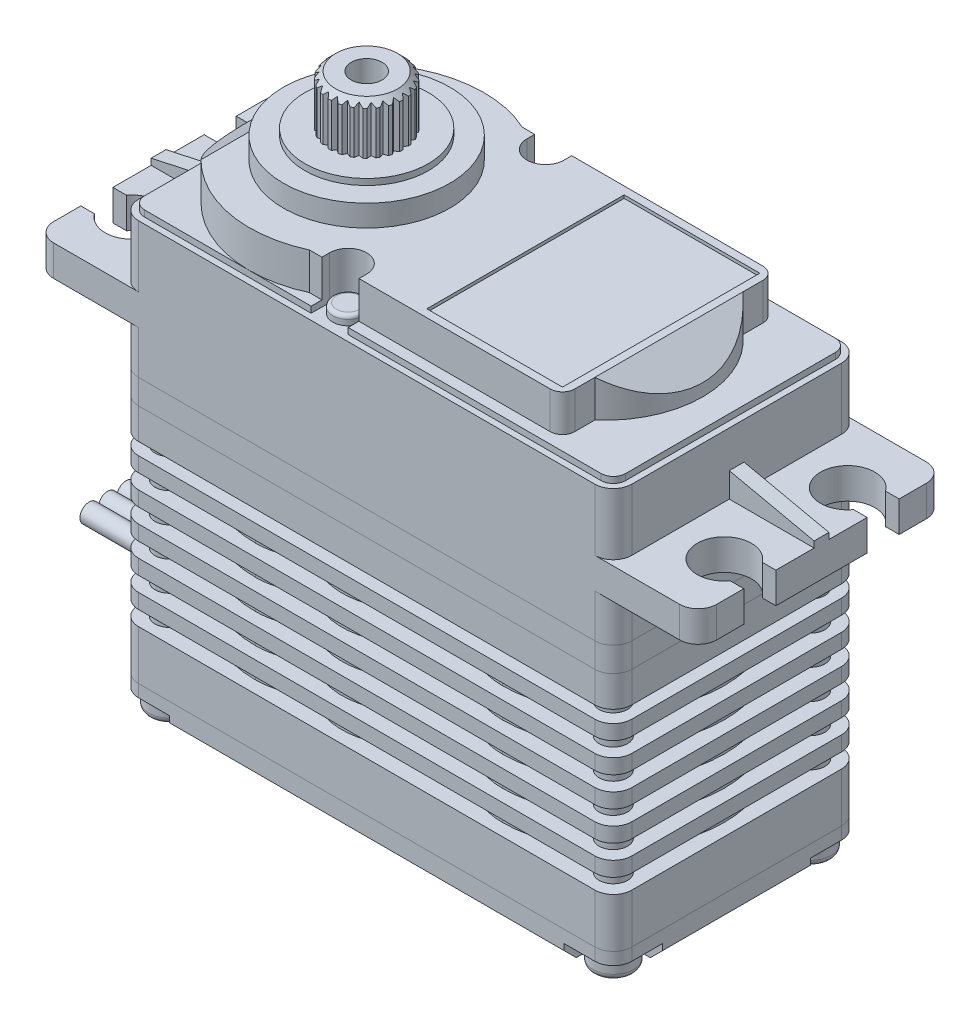
SolidWorks part; units mm, degrees
ref_plane "Front Plane" through (0, 0, 0) normal (0, 0, 1) x (1, 0, 0)
ref_plane "Top Plane" through (0, 0, 0) normal (0, 1, 0) x (1, 0, 0)
ref_plane "Right Plane" through (0, 0, 0) normal (1, 0, 0) x (0, 0, -1)
sketch "Sketch3" plane through (0, 0, 0) normal (0, 1, 0) x (1, 0, 0)
  line L1 (-20, -10) -> (20, -10)
  line L2 (-20, -10) -> (-20, 10)
  line L3 (-20, 10) -> (20, 10)
  line L4 (20, -10) -> (20, 10)
  line L5 (-20, -10) -> (20, 10) construction
  line L6 (-20, 10) -> (20, -10) construction
  point P0 (0, 0)
  dimension "D1" = 40
  dimension "D2" = 20
extrude "Boss-Extrude2" add sketch "Sketch3" against normal blind 27.5 and the other way blind 7.5
sketch "Sketch4" plane through (0, 0, 0) normal (0, 1, 0) x (1, 0, 0)
  line L0 (20, 10) -> (-20, 10) construction
  line L1 (-26.875, -10) -> (26.875, -10)
  line L2 (-26.875, -10) -> (-26.875, 10)
  line L3 (-26.875, 10) -> (26.875, 10)
  line L4 (26.875, -10) -> (26.875, 10)
  line L5 (-26.875, -10) -> (26.875, 10) construction
  line L6 (-26.875, 10) -> (26.875, -10) construction
  point P0 (0, 0)
  dimension "D1" = 53.75
extrude "Boss-Extrude3" add sketch "Sketch4" along normal blind 2.5
sketch "Sketch5" plane through (0, 2.5, 0) normal (0, 1, 0) x (1, 0, 0)
  line L1 (-24, -5) -> (24, -5) construction
  line L2 (-24, -5) -> (-24, 5) construction
  line L3 (-24, 5) -> (24, 5) construction
  line L4 (24, -5) -> (24, 5) construction
  line L5 (-24, -5) -> (24, 5) construction
  line L6 (-24, 5) -> (24, -5) construction
  circle A0 centre (-24, 5) radius 2.2
  circle A1 centre (-24, -5) radius 2.2
  circle A2 centre (24, -5) radius 2.2
  circle A3 centre (24, 5) radius 2.2
  point P0 (0, 0)
  dimension "D3" = 4.4
  dimension "D1" = 10
  dimension "D2" = 48
extrude "Cut-Extrude2" cut sketch "Sketch5" against normal through all
sketch "Sketch6" plane through (0, 2.5, 0) normal (0, 1, 0) x (1, 0, 0)
  line L0 (-24, 5) -> (-26.875, 5) construction
  line L1 (-26.875, 10) -> (-26.875, -10) construction
  line L2 (-24, 3.7) -> (-26.875, 3.7)
  line L3 (-24, 6.3) -> (-26.875, 6.3)
  line L4 (-24, -5) -> (-26.875, -5) construction
  line L5 (-24, -6.3) -> (-26.875, -6.3)
  line L6 (-24, -3.7) -> (-26.875, -3.7)
  line L7 (24, -5) -> (26.875, -5) construction
  line L8 (26.875, -10) -> (26.875, 10) construction
  line L9 (24, -3.7) -> (26.875, -3.7)
  line L10 (24, -6.3) -> (26.875, -6.3)
  line L11 (24, 5) -> (26.875, 5) construction
  line L12 (24, 6.3) -> (26.875, 6.3)
  line L13 (24, 3.7) -> (26.875, 3.7)
  arc A0 (-24, 3.7) -> (-24, 6.3) centre (-24, 5) ccw
  arc A1 (-26.875, 6.3) -> (-26.875, 3.7) centre (-26.875, 5) ccw
  arc A2 (-24, -6.3) -> (-24, -3.7) centre (-24, -5) ccw
  arc A3 (-26.875, -3.7) -> (-26.875, -6.3) centre (-26.875, -5) ccw
  arc A4 (24, -3.7) -> (24, -6.3) centre (24, -5) ccw
  arc A5 (26.875, -6.3) -> (26.875, -3.7) centre (26.875, -5) ccw
  arc A6 (24, 6.3) -> (24, 3.7) centre (24, 5) ccw
  arc A7 (26.875, 3.7) -> (26.875, 6.3) centre (26.875, 5) ccw
  point P5 (-25.4375, 5)
  point P10 (-25.4375, -5)
  point P18 (25.4375, -5)
  point P28 (25.4375, 5)
  dimension "D1" = 2.6
extrude "Cut-Extrude3" cut sketch "Sketch6" against normal through all
fillet "Fillet1" radius 1.5 4 edges at (26.875, 1.25, -10) (26.875, 1.25, 10) (-26.875, 1.25, 10) (-26.875, 1.25, -10)
fillet "Fillet2" radius 1.5 8 edges at (20, -13.75, -10) (20, 5, -10) (20, -13.75, 10) (20, 5, 10) (-20, 5, -10) (-20, -13.75, -10) (-20, 5, 10) (-20, -13.75, 10)
sketch "Sketch7" plane through (0, 7.5, 0) normal (0, 1, 0) x (1, 0, 0)
  line L8 (19.5, -8.5) -> (19.5, 8.5)
  line L9 (18.5, 9.5) -> (-18.5, 9.5)
  line L10 (-19.5, 8.5) -> (-19.5, -8.5)
  line L11 (-18.5, -9.5) -> (18.5, -9.5)
  line L12 (19.5, -8.5) -> (19.5, 8.5)
  line L13 (18.5, 9.5) -> (-18.5, 9.5)
  line L14 (-19.5, 8.5) -> (-19.5, -8.5)
  line L15 (-18.5, -9.5) -> (18.5, -9.5)
  arc A8 (19.5, 8.5) -> (18.5, 9.5) centre (18.5, 8.5) ccw
  arc A9 (-18.5, 9.5) -> (-19.5, 8.5) centre (-18.5, 8.5) ccw
  arc A10 (-19.5, -8.5) -> (-18.5, -9.5) centre (-18.5, -8.5) ccw
  arc A11 (18.5, -9.5) -> (19.5, -8.5) centre (18.5, -8.5) ccw
  arc A12 (19.5, 8.5) -> (18.5, 9.5) centre (18.5, 8.5) ccw
  arc A13 (-18.5, 9.5) -> (-19.5, 8.5) centre (-18.5, 8.5) ccw
  arc A14 (-19.5, -8.5) -> (-18.5, -9.5) centre (-18.5, -8.5) ccw
  arc A15 (18.5, -9.5) -> (19.5, -8.5) centre (18.5, -8.5) ccw
  dimension "D1" = 0.5
extrude "Boss-Extrude4" add sketch "Sketch7" along normal blind 0.5
sketch "Sketch8" plane through (0, 0, 0) normal (0, 0, 1) x (1, 0, 0)
  line L0 (20, 4.5) -> (26.875, 3)
  line L1 (20, 7.5) -> (20, 2.5) construction
  line L2 (26.875, 3) -> (26.875, 2.5)
  line L3 (26.875, 2.5) -> (20, 2.5)
  line L4 (20, 2.5) -> (20, 4.5)
  line L5 (18.5, 0) -> (25.375, 0) construction
  line L6 (-26.875, 2.5) -> (-26.875, 3)
  line L7 (-26.875, 3) -> (-20, 4.5)
  line L8 (-20, 2.5) -> (-20, 7.5) construction
  line L9 (-20, 4.5) -> (-20, 2.5)
  line L10 (-20, 2.5) -> (-26.875, 2.5)
  dimension "D1" = 0.5
  dimension "D2" = 4.5
extrude "Boss-Extrude5" add sketch "Sketch8" along normal mid plane 1.2
sketch "Sketch9" plane through (0, 8, 0) normal (0, 1, 0) x (1, 0, 0)
  line L0 (-19.5, 8.5) -> (-19.5, -8.5) construction
  line L1 (18.5, 9.5) -> (-18.5, 9.5) construction
  line L2 (-18.5, -9.5) -> (18.5, -9.5) construction
  line L3 (-6.0176, 8.625) -> (14.5, 8.625)
  line L4 (14.5, 8.625) -> (14.5, 6)
  line L5 (-6.0176, -8.625) -> (14.5, -8.625)
  line L6 (14.5, -8.625) -> (14.5, -6)
  line L7 (-19.5, 0) -> (17.25, 0) construction
  line L8 (20, -8.5) -> (20, 8.5) construction
  arc A0 (-6.0176, 8.625) -> (-6.0176, -8.625) centre (-10, 0) ccw
  arc A1 (14.5, 6) -> (14.5, -6) centre (9.3295, 0) cw
  dimension "D1" = 17.25
  dimension "D2" = 12
  dimension "D3" = 36.75
  dimension "D4" = 5.5
extrude "Boss-Extrude6" add sketch "Sketch9" along normal blind 3
sketch "Sketch10" plane through (0, 11, 0) normal (0, 1, 0) x (1, 0, 0)
  circle A0 centre (-10, 0) radius 6.75
  dimension "D1" = 13.5
extrude "Boss-Extrude7" add sketch "Sketch10" along normal blind 1.75
sketch "Sketch11" plane through (0, 0, 0) normal (0, 0, 1) x (1, 0, 0)
  line L0 (14.5, 11) -> (17.25, 9)
  line L1 (17.25, 8) -> (17.25, 11) construction
  line L2 (17.25, 9) -> (17.25, 11)
  line L3 (17.25, 11) -> (14.5, 11) construction
  line L4 (17.25, 11) -> (14.5, 11)
  line L5 (-10, 8) -> (18.5, 8) construction
  line L6 (-16.75, 11) -> (-19.5, 9)
  line L7 (-19.5, 9) -> (-19.5, 11)
  line L8 (-19.5, 11) -> (-16.75, 11)
  line L9 (-18.5, 8) -> (-10, 8) construction
  dimension "D1" = 1
  dimension "D2" = 1
extrude "Cut-Extrude4" cut sketch "Sketch11" against normal through all both and the other way through all
fillet "Fillet3" radius 1 2 edges at (14.5, 9.5, -8.625) (14.5, 9.5, 8.625)
sketch "Sketch12" plane through (0, 12.75, 0) normal (0, 1, 0) x (1, 0, 0)
  circle A0 centre (-10, 0) radius 5
  dimension "D1" = 10
extrude "Boss-Extrude8" add sketch "Sketch12" along normal blind 0.5
ref_plane "Plane2" through (0, -3.5, 0) normal (0, 1, 0) x (1, 0, 0)
split "Split1" trim tools "Plane2" bodies to split 115 resulting bodies 116 117
ref_plane "Plane3" through (0, -5.5, 0) normal (0, 1, 0) x (1, 0, 0)
split "Split2" trim tools "Plane3" bodies to split 117 resulting bodies 118 119
ref_plane "Plane4" through (0, -25, 0) normal (0, -1, 0) x (-1, 0, 0)
split "Split3" trim tools "Plane4" bodies to split 119 resulting bodies 120 121
sketch "Sketch13" plane through (0, 11, 0) normal (0, 1, 0) x (1, 0, 0)
  line L0 (-3.5, 8) -> (-3.5, -8) construction
  line L1 (-3.5, 0) -> (-10, 0) construction
  line L2 (14.5, -7.625) -> (14.5, -6) construction
  line L3 (-3.5, -8) -> (-3.5, -9.5) construction
  line L5 (-2, -8) -> (-2, -9.5)
  line L6 (-5, -8) -> (-5, -9.5)
  line L7 (-3.5, 8) -> (-3.5, 9.5) construction
  line L9 (-5, 8) -> (-5, 9.5)
  line L10 (-2, 8) -> (-2, 9.5)
  line L11 (18.5, 9.5) -> (-18.5, 9.5) construction
  circle A0 centre (-3.5, 8) radius 1.5 construction
  circle A1 centre (-3.5, -8) radius 1.5 construction
  arc A2 (-2, -8) -> (-5, -8) centre (-3.5, -8) ccw
  arc A3 (-5, -9.5) -> (-2, -9.5) centre (-3.5, -9.5) ccw
  arc A4 (-5, 8) -> (-2, 8) centre (-3.5, 8) ccw
  arc A5 (-2, 9.5) -> (-5, 9.5) centre (-3.5, 9.5) ccw
  point P12 (-3.5, -8.75)
  point P17 (-3.5, 8.75)
  dimension "D2" = 3
  dimension "D1" = 16
  dimension "D3" = 18
extrude "Cut-Extrude5" cut sketch "Sketch13" against normal up to surface (3.5 mm away) up to face at (0, 7.5, 0)
sketch "Sketch15" plane through (0, -27.5, 0) normal (0, -1, 0) x (1, 0, 0)
  line L0 (-20, -8.5) -> (-20, 8.5) construction
  line L1 (-20, 6) -> (-18, 6)
  line L2 (-20, 6) -> (-20, 10)
  line L3 (-20, 10) -> (-16, 10)
  line L4 (-16, 8) -> (-16, 10)
  line L5 (-18.5, 10) -> (18.5, 10) construction
  line L6 (18.5, -10) -> (-18.5, -10) construction
  line L7 (-20, -6) -> (-18, -6)
  line L8 (-20, -6) -> (-20, -10)
  line L9 (-20, -10) -> (-16, -10)
  line L10 (-16, -8) -> (-16, -10)
  line L11 (20, -8.5) -> (20, 8.5) construction
  line L12 (16, -10) -> (20, -10)
  line L13 (16, -10) -> (16, -8)
  line L14 (18, -6) -> (20, -6)
  line L15 (20, -10) -> (20, -6)
  line L17 (20, 6) -> (18, 6)
  line L18 (20, 6) -> (20, 10)
  line L19 (20, 10) -> (16, 10)
  line L20 (16, 8) -> (16, 10)
  arc A0 (18, 6) -> (16, 8) centre (18, 8) cw
  arc A1 (16, -8) -> (18, -6) centre (18, -8) cw
  arc A2 (-18, -6) -> (-16, -8) centre (-18, -8) cw
  arc A3 (-18, 6) -> (-16, 8) centre (-18, 8) ccw
  dimension "D3" = 2
  dimension "D1" = 4
  dimension "D2" = 4
extrude "Cut-Extrude6" cut sketch "Sketch15" against normal blind 1.5
chamfer "Chamfer3" distance 1 angle 45 4 edges at (20, -27.5, 0) (0, -27.5, 10) (0, -27.5, -10) (-20, -27.5, 0)
sketch "Sketch16" plane through (-20, 0, 0) normal (-1, 0, 0) x (0, 0, 1)
  line L0 (0, -21.5) -> (0, 0) construction
  line L1 (-3.5, -21.5) -> (3.5, -21.5)
  line L2 (-3.5, -21.5) -> (-3.5, -25.5)
  line L3 (-3.5, -25.5) -> (3.5, -25.5)
  line L4 (3.5, -21.5) -> (3.5, -25.5)
  line L5 (6, -27.5) -> (-6, -27.5) construction
  dimension "D1" = 4
  dimension "D2" = 2
  dimension "D3" = 7
extrude "Boss-Extrude9" add sketch "Sketch16" along normal blind 1 separate body
sketch "Sketch17" plane through (-21, 0, 0) normal (-1, 0, 0) x (0, 0, 1)
  line L8 (-3.25, -21.75) -> (-3.25, -25.25)
  line L9 (-3.25, -25.25) -> (3.25, -25.25)
  line L10 (3.25, -25.25) -> (3.25, -21.75)
  line L11 (3.25, -21.75) -> (-3.25, -21.75)
  line L12 (-3.25, -21.75) -> (-3.25, -25.25)
  line L13 (-3.25, -25.25) -> (3.25, -25.25)
  line L14 (3.25, -25.25) -> (3.25, -21.75)
  line L15 (3.25, -21.75) -> (-3.25, -21.75)
  dimension "D1" = 0.25
ref_plane "Plane5" through (-26, 0, 0) normal (-1, 0, 0) x (0, 0, 1)
sketch "Sketch18" plane through (-26, 0, 0) normal (-1, 0, 0) x (0, 0, 1)
  line L0 (-3.5, -25.5) -> (3.5, -21.5) construction
  line L2 (-2.5, -24.75) -> (2.5, -24.75)
  line L3 (-2.5, -24.75) -> (-2.5, -22.25)
  line L4 (-2.5, -22.25) -> (2.5, -22.25)
  line L5 (2.5, -24.75) -> (2.5, -22.25)
  line L6 (-2.5, -24.75) -> (2.5, -22.25) construction
  line L7 (-2.5, -22.25) -> (2.5, -24.75) construction
  point P4 (0, -23.5)
  dimension "D1" = 5
  dimension "D2" = 2.5
loft "Loft1" add profiles "Sketch17", "Sketch18" connector at (-21, -21.75, -3.25) connector at (-26, -22.25, -2.5)
sketch "Sketch19" plane through (-26, 0, 0) normal (-1, 0, 0) x (0, 0, 1)
  line L0 (0, -24.75) -> (0, -23.5) construction
  line L1 (-2.5, -24.75) -> (2.5, -24.75) construction
  line L2 (0, -23.5) -> (0, -22.25) construction
  line L3 (2.5, -22.25) -> (-2.5, -22.25) construction
  circle A0 centre (0, -23.5) radius 0.75
  circle A1 centre (1.5, -23.5) radius 0.75
  circle A2 centre (-1.5, -23.5) radius 0.75
  dimension "D1" = 1.5
extrude "Boss-Extrude11" add sketch "Sketch19" along normal blind 5 separate body contours A2 | A0 | A1 region at (-26, -23.5, 0) region at (-26, -23.5, -1.5) region at (-26, -23.5, 1.5)
sketch "Sketch20" plane through (0, 11, 0) normal (0, 1, 0) x (1, 0, 0)
  line L0 (-10, 0) -> (2.875, 0) construction
  line L1 (2.875, -8) -> (13.875, -8)
  line L2 (2.875, -8) -> (2.875, 8)
  line L3 (2.875, 8) -> (13.875, 8)
  line L4 (13.875, -8) -> (13.875, 8)
  line L5 (2.875, -8) -> (13.875, 8) construction
  line L6 (2.875, 8) -> (13.875, -8) construction
  line L7 (8.375, 8) -> (8.375, 8.625) construction
  line L8 (13.5, 8.625) -> (-2, 8.625) construction
  line L9 (13.875, 6.9566) -> (14.5, 6.9566) construction
  line L10 (14.5, 6) -> (14.5, 7.625) construction
  point P0 (8.375, 0)
  dimension "D1" = 16
  dimension "D2" = 11
extrude "Cut-Extrude7" cut sketch "Sketch20" against normal blind 0.25
sketch "Sketch21" plane through (0, 13.25, 0) normal (0, 1, 0) x (1, 0, 0)
  circle A0 centre (-10, 0) radius 3
  dimension "D1" = 6
extrude "Boss-Extrude12" add sketch "Sketch21" along normal blind 4 separate body
chamfer "Chamfer4" distance 0.5 angle 45 1 edges at (-10, 17.25, 3)
sketch "Sketch22" plane through (0, 17.25, 0) normal (0, 1, 0) x (1, 0, 0)
  line L0 (-10.25, 2.9896) -> (-10, 2.75)
  line L1 (-10, 2.75) -> (-9.75, 2.9896)
  line L2 (-10, 0) -> (-10, 2.75) construction
  line L3 (-10, 2.75) -> (-10, 3) construction
  arc A1 (-9.75, 2.9896) -> (-10.25, 2.9896) centre (-10, 0) ccw
  circle A2 centre (-10, 0) radius 3 construction
  dimension "D1" = 0.25
  dimension "D2" = 0.5
extrude "Cut-Extrude8" cut sketch "Sketch22" against normal up to surface (4 mm away) up to face at (-10, 13.25, 5)
pattern_circular "CirPattern1" count 25 over 360 about axis through (-10, 17.25, 0) along (0, -1, 0) of "Cut-Extrude8"
hole_wizard "M3x0.5 Tapped Hole1" positions "Sketch23" profile "Sketch25" tap size "M3x0.5" standard "ANSI Metric"
sketch "Sketch23" plane through (0, 17.25, 0) normal (0, 1, 0) x (1, 0, 0)
  point P0 (-10, 0)
sketch "Sketch25" plane through (-10, 17.25, 0) normal (1, 0, 0) x (0, 0, 1)
  line L0 (0, 0) -> (0, 9.2511)
  line L1 (0, 9.2511) -> (1.25, 8.5)
  line L2 (1.25, 8.5) -> (1.25, 0)
  line L5 (1.25, 0) -> (0, 0)
  line L10 (0, 9.2511) -> (-1.25, 8.5) construction
  line L11 (0, -6.35) -> (0, 107.95) construction
  dimension "Tap Drill Dia." = 2.5
  dimension "Tap Drill Depth" = 8.5
  dimension "Drill Angle" = 118
ref_plane "Plane6" through (0, -21, 0) normal (0, -1, 0) x (-1, 0, 0)
sketch "Sketch26" plane through (0, -26, 0) normal (0, -1, 0) x (1, 0, 0)
  line L0 (18, -8) -> (18, -10) construction
  line L1 (16, -10) -> (18.5, -10) construction
  line L2 (18, -8) -> (20, -8) construction
  line L3 (20, -8.5) -> (20, -6) construction
  line L5 (-18, 8) -> (18, 8) construction
  line L6 (-18, 8) -> (-18, -8) construction
  line L7 (-18, -8) -> (18, -8) construction
  line L8 (18, 8) -> (18, -8) construction
  line L9 (-18, 8) -> (18, -8) construction
  line L10 (-18, -8) -> (18, 8) construction
  circle A0 centre (18, -8) radius 1.65
  arc A1 (18, -6) -> (16, -8) centre (18, -8) ccw construction
  circle A2 centre (-18, -8) radius 1.65
  circle A3 centre (-18, 8) radius 1.65
  circle A4 centre (18, 8) radius 1.65
  point P8 (0, 0)
  dimension "D1" = 3.3
extrude "Boss-Extrude13" add sketch "Sketch26" along normal up to surface (1.5 mm away) up to face at (0, -27.5, 0)
fillet "Fillet4" radius 0.5 4 edges at (-18, -27.5, -9.65) (-18, -27.5, 6.35) (18, -27.5, 6.35) (18, -27.5, -9.65)
sketch "Sketch27" plane through (0, -21, 0) normal (0, -1, 0) x (-1, 0, 0)
  line L0 (0, 0) -> (-50000, 0) construction
  line L2 (-16, -9) -> (16, -9) construction
  line L3 (-19, 6) -> (-19, -6) construction
  line L4 (6.5, -8.5) -> (6.5, -9) construction
  line L5 (-3.5, -7.5) -> (-3.5, -9) construction
  line L6 (20, -8.5) -> (20, 8.5) construction
  line L11 (18.5, 10) -> (-18.5, 10)
  line L12 (20, -8.5) -> (20, 8.5)
  line L13 (-18.5, -10) -> (18.5, -10)
  line L14 (-20, 8.5) -> (-20, -8.5)
  line L15 (18.5, 10) -> (-18.5, 10)
  line L16 (20, -8.5) -> (20, 8.5)
  line L17 (-18.5, -10) -> (18.5, -10)
  line L18 (-20, 8.5) -> (-20, -8.5)
  circle A0 centre (-18, 8) radius 1.15 construction
  circle A1 centre (-18, -8) radius 1.15 construction
  circle A2 centre (18, -8) radius 1.15 construction
  circle A3 centre (18, 8) radius 1.15 construction
  circle A4 centre (-18, 8) radius 1.15
  circle A5 centre (-18, -8) radius 1.15
  circle A6 centre (18, -8) radius 1.15
  circle A7 centre (18, 8) radius 1.15
  arc A8 (10, 9) -> (10, -9) centre (10, 0) cw
  arc A9 (10, -9) -> (8.4576, -8.7797) centre (10, -3.4916) cw
  arc A10 (8.4576, -8.7797) -> (4.5424, -8.7797) centre (6.5, -15.4916) ccw
  arc A11 (4.5424, -8.7797) -> (0.5862, -8.443) centre (3, -3.4916) cw
  arc A12 (0.5862, -8.443) -> (-7.5862, -8.443) centre (-3.5, -16.8249) ccw
  arc A13 (-7.5862, -8.443) -> (-10, -9) centre (-10, -3.4916) cw
  arc A14 (-10, -9) -> (-10, 9) centre (-10, 0) cw
  arc A15 (10, 9) -> (8.4576, 8.7797) centre (10, 3.4916) ccw
  arc A16 (8.4576, 8.7797) -> (4.5424, 8.7797) centre (6.5, 15.4916) cw
  arc A17 (4.5424, 8.7797) -> (0.5862, 8.443) centre (3, 3.4916) ccw
  arc A18 (0.5862, 8.443) -> (-7.5862, 8.443) centre (-3.5, 16.8249) cw
  arc A19 (-7.5862, 8.443) -> (-10, 9) centre (-10, 3.4916) ccw
  arc A24 (-18.5, 10) -> (-20, 8.5) centre (-18.5, 8.5) ccw
  arc A25 (20, 8.5) -> (18.5, 10) centre (18.5, 8.5) ccw
  arc A26 (18.5, -10) -> (20, -8.5) centre (18.5, -8.5) ccw
  arc A27 (-20, -8.5) -> (-18.5, -10) centre (-18.5, -8.5) ccw
  arc A28 (-18.5, 10) -> (-20, 8.5) centre (-18.5, 8.5) ccw
  arc A29 (20, 8.5) -> (18.5, 10) centre (18.5, 8.5) ccw
  arc A30 (18.5, -10) -> (20, -8.5) centre (18.5, -8.5) ccw
  arc A31 (-20, -8.5) -> (-18.5, -10) centre (-18.5, -8.5) ccw
  dimension "D1" = 10
  dimension "D2" = 0.5
  dimension "D3" = 1.5
  dimension "D4" = 13.5
  dimension "D5" = 23.5
  dimension "D6" = 0
extrude "Cut-Extrude9" cut sketch "Sketch27" against normal blind 13
sketch "Sketch28" plane through (0, -21, 0) normal (0, 1, 0) x (1, 0, 0)
  line L4 (18.5, 10) -> (-18.5, 10)
  line L5 (-20, 8.5) -> (-20, -8.5)
  line L6 (-18.5, -10) -> (18.5, -10)
  line L7 (20, -8.5) -> (20, 8.5)
  line L8 (18.5, 10) -> (-18.5, 10)
  line L9 (-20, 8.5) -> (-20, -8.5)
  line L10 (-18.5, -10) -> (18.5, -10)
  line L11 (20, -8.5) -> (20, 8.5)
  arc A4 (20, 8.5) -> (18.5, 10) centre (18.5, 8.5) ccw
  arc A5 (-18.5, 10) -> (-20, 8.5) centre (-18.5, 8.5) ccw
  arc A6 (-20, -8.5) -> (-18.5, -10) centre (-18.5, -8.5) ccw
  arc A7 (18.5, -10) -> (20, -8.5) centre (18.5, -8.5) ccw
  arc A8 (20, 8.5) -> (18.5, 10) centre (18.5, 8.5) ccw
  arc A9 (-18.5, 10) -> (-20, 8.5) centre (-18.5, 8.5) ccw
  arc A10 (-20, -8.5) -> (-18.5, -10) centre (-18.5, -8.5) ccw
  arc A11 (18.5, -10) -> (20, -8.5) centre (18.5, -8.5) ccw
  dimension "D1" = 0
extrude "Boss-Extrude14" add sketch "Sketch28" along normal blind 1.2 from offset 1.2
pattern_linear "LPattern1" count 5 spacing 2.4 along (0, 1, 0) of "Boss-Extrude14"
sketch "Sketch29" plane through (0, 7.5, 0) normal (0, 1, 0) x (1, 0, 0)
  circle A0 centre (-3.5, -8) radius 1.25
  circle A1 centre (-3.5, 8) radius 1.25
  dimension "D1" = 2.5
extrude "Boss-Extrude15" add sketch "Sketch29" along normal blind 0.75
fillet "Fillet5" radius 0.3 2 edges at (-3.5, 8.25, -6.75) (-3.5, 8.25, 9.25)
